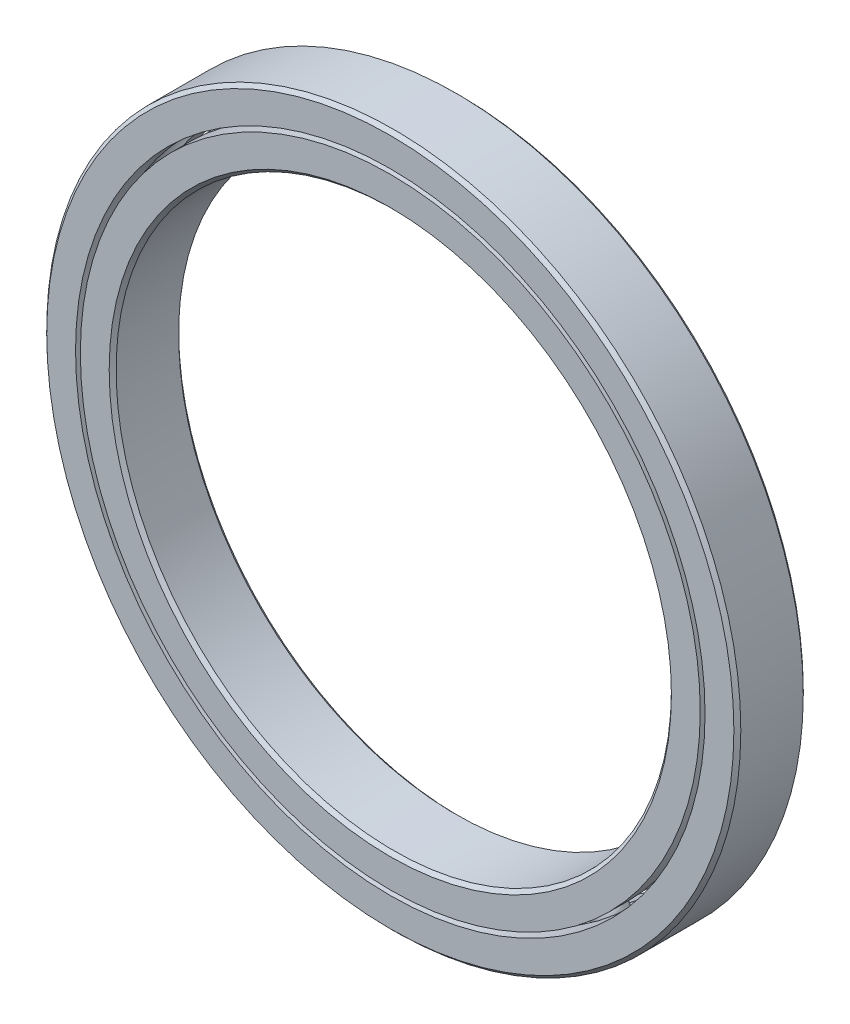
SolidWorks part; units mm, degrees
ref_plane "Front Plane" through (0, 0, 0) normal (0, 0, 1) x (1, 0, 0)
ref_plane "Top Plane" through (0, 0, 0) normal (0, 1, 0) x (1, 0, 0)
ref_plane "Right Plane" through (0, 0, 0) normal (1, 0, 0) x (0, 0, -1)
sketch "Sketch1" plane through (0, 0, 0) normal (1, 0, 0) x (0, 0, -1)
  line L0 (-3.175, 0) -> (3.175, 0) construction
  line L1 (0, 31.75) -> (0, -31.75) construction
  line L2 (2.8575, 31.75) -> (-2.8575, 31.75)
  line L3 (-2.8575, 31.75) -> (-3.175, 31.4325)
  line L4 (-3.175, 31.4325) -> (-3.175, 28.7948)
  line L5 (-3.175, 28.7948) -> (-1.4111, 28.7948)
  line L6 (3.175, 28.7948) -> (1.4111, 28.7948)
  line L7 (3.175, 31.4325) -> (3.175, 28.7948)
  line L8 (2.8575, 31.75) -> (3.175, 31.4325)
  line L9 (0, 31.75) -> (0, 28.575) construction
  line L10 (0, 28.575) -> (0, 25.4) construction
  arc A0 (-1.4111, 28.7948) -> (1.4111, 28.7948) centre (0, 28.575) cw
  point P14 (0, 25.4)
  dimension "Width" = 6.35
  dimension "OD" = 63.5
  dimension "D1" = 45
  dimension "D2" = 0.3175
  dimension "Shaft Dia" = 50.8
  dimension "D3" = 2.8222
  dimension "D4" = 0.2198
revolve "Revolve1" add sketch "Sketch1" angle 360 about L0
sketch "Sketch3" plane through (0, 0, 0) normal (1, 0, 0) x (0, 0, -1)
  line L0 (-3.175, 28.3552) -> (-1.4111, 28.3552)
  line L1 (0, 31.75) -> (0, -31.75) construction
  line L2 (-3.175, 31.4325) -> (-3.175, 28.7948) construction
  line L3 (-3.175, 28.3552) -> (-3.175, 25.7175)
  line L4 (-2.8575, 31.75) -> (-3.175, 31.4325) construction
  line L5 (-3.175, 25.7175) -> (-2.8575, 25.4)
  line L6 (-2.8575, 25.4) -> (2.8575, 25.4)
  line L7 (2.8575, 31.75) -> (2.8575, -31.75) construction
  line L8 (2.8575, 25.4) -> (3.175, 25.7175)
  line L9 (3.175, -31.4325) -> (3.175, 31.4325) construction
  line L10 (3.175, 25.7175) -> (3.175, 28.3552)
  line L11 (3.175, 28.3552) -> (1.4111, 28.3552)
  line L13 (2.8575, 31.75) -> (3.175, 31.4325) construction
  arc A0 (1.4111, 28.7948) -> (-1.4111, 28.7948) centre (0, 28.575) ccw construction
  arc A1 (1.4111, 28.3552) -> (-1.4111, 28.3552) centre (0, 28.575) cw
revolve "Revolve3" add sketch "Sketch3" angle 360 about L0
sketch "Sketch4" plane through (0, 0, 0) normal (1, 0, 0) x (0, 0, -1)
  line L0 (-1.4281, 28.575) -> (1.4281, 28.575)
  arc A2 (-1.4281, 28.575) -> (1.4281, 28.575) centre (0, 28.575) cw
  arc A3 (1.4111, 28.7948) -> (-1.4111, 28.7948) centre (0, 28.575) ccw construction
revolve "Revolve4" add sketch "Sketch4" angle 360 about L0
ref_axis "Axis1" through (0, 0, -3.175) along (0, 0, 1)
pattern_circular "CirPattern1" count 10 every 36 about axis through (0, 0, -3.175) along (0, 0, 1) of bodies 104
equation "\"D2@Sketch1\" = \"Width@Sketch1\"*.05"
equation "\"D3@Sketch1\" = \"Width@Sketch1\"/2.25"
equation "\"D4@Sketch1\" = (((\"OD@Sketch1\"-\"Width@Sketch1\")/2)/3.25)*.025"
equation "\"D2@CirPattern1\" = 360/\"Balls@CirPattern1\""
